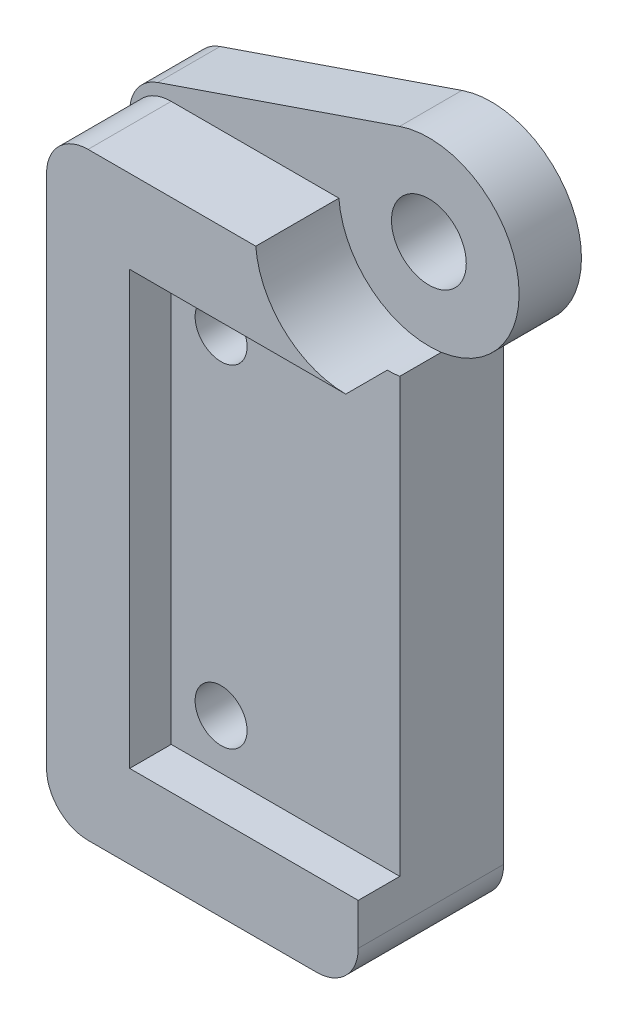
SolidWorks part; units mm, degrees
ref_plane "Front Plane" through (0, 0, 0) normal (0, 0, 1) x (1, 0, 0)
ref_plane "Top Plane" through (0, 0, 0) normal (0, 1, 0) x (1, 0, 0)
ref_plane "Right Plane" through (0, 0, 0) normal (1, 0, 0) x (0, 0, -1)
sketch "Sketch1" plane through (0, 0, 0) normal (0, 0, 1) x (1, 0, 0)
  line L0 (-38, -8) -> (-38, 8) construction
  line L1 (40, -10) -> (-40, -10)
  line L2 (40, -10) -> (40, 10)
  line L3 (40, 10) -> (-40, 10)
  line L4 (-40, -10) -> (-40, 10)
  line L5 (40, -10) -> (-40, 10) construction
  line L6 (40, 10) -> (-40, -10) construction
  line L7 (-40.4, 10.4) -> (-40.4, -10.4)
  line L8 (-40.4, -10.4) -> (-29.4, -10.4)
  line L9 (-29.4, -10.4) -> (-29.4, -14.4)
  line L10 (-29.4, -14.4) -> (-44.4, -14.4)
  line L11 (-44.4, -14.4) -> (-44.4, 14.4)
  line L12 (-44.4, 14.4) -> (-29.4, 14.4)
  line L13 (-29.4, 14.4) -> (-29.4, 10.4)
  line L14 (-29.4, 10.4) -> (-40.4, 10.4)
  line L15 (-29.4, -10.4) -> (-29.4, 10.4)
  line L17 (-44.4, 14.4) -> (-31.4083, 18.8528)
  circle A0 centre (-38, 8) radius 1.25
  circle A1 centre (-38, -8) radius 1.25
  circle A2 centre (-30, 14.7437) radius 1.8
  circle A3 centre (0, -6) radius 2.75 construction
  circle A4 centre (-30, 14.7437) radius 4.3437
  circle A5 centre (-38, 8) radius 2.3
  circle A6 centre (-38, -8) radius 2.3
  point P0 (0, 0)
  point P8 (-38, 0)
  point P13 (-29.4, 0)
  dimension "D5" = 2.5
  dimension "D12" = 3.6
  dimension "D13" = 16
  dimension "D14" = 5.5
  dimension "D15" = 20.7437
  dimension "D16" = 4.6
  dimension "D1" = 16
  dimension "D2" = 38
  dimension "D3" = 80
  dimension "D4" = 20
  dimension "D6" = 0.4
  dimension "D7" = 0.4
  dimension "D8" = 4
  dimension "D9" = 4
  dimension "D10" = 15
  dimension "D11" = 30
extrude "Boss-Extrude1" add sketch "Sketch1" along normal blind 3 contours L14 L13 A2 L12 L11 L10 L9 L8 L7 | A6 L4 A5 L3 L15 L14 L7 L8 L1 | A6 L4 L1 | A6 L1 L15 L3 A5 L4 | L13 L17 L12 A2 | A5 L3 L4 | L12 A4 L13 A2 | A4 L14 L13 | A4 L17 L12 region at (-29.6353, -10.2, 0) region at (-34.1181, 0, 0) region at (-29.7247, -12.4, 0) region at (-39.7386, -9.7386, 0) region at (-29.5499, 10.4125, 0) region at (-39.7386, 9.7386, 0) region at (-31.7182, 12.4313, 0) region at (-29.2774, 11.7441, 0) region at (-37.3258, 15.7206, 0)
extrude "Boss-Extrude2" add sketch "Sketch1<4>" along normal blind 2 from surface contours L14 L13 L12 L11 L10 L9 L8 L7 | A6 L1 L15 L3 A5 L4 | A6 L4 A5 L3 L15 L14 L7 L8 L1 | L3 A5 L4 A0 | L4 A5 | L3 A5 | A5 L3 L4 | A6 L4 L1 | L4 A6 L1 A1 | L4 A6 | L1 A6 | A4 L14 L13 region at (-29.6353, -10.2, 0) region at (-34.1181, 0, 0) region at (-38, -10.1207, 0) region at (-38, -9.9392, 0) region at (-29.7247, -12.4, 0) region at (-39.7386, -9.7386, 0) region at (-36.0648, 9.1265, 0) region at (-38, 10.1207, 0) region at (-29.5499, 10.4125, 0) region at (-40.1207, -8, 0) region at (-39.7386, 9.7386, 0) region at (-40.1207, 8, 0) starting at face at (-35.7, 8, 3)
sketch "Sketch1<4>" plane through (0, 0, 0) normal (0, 0, 1) x (1, 0, 0) same geometry as "Sketch1"
extrude "Boss-Extrude3" add sketch "Sketch1<5>" along normal blind 2 from surface contours A4 L12 L11 L10 L9 L8 L7 L14 region at (-29.7247, -12.4, 0) starting at face at (-36.75, -8, 5)
sketch "Sketch1<5>" plane through (0, 0, 0) normal (0, 0, 1) x (1, 0, 0) same geometry as "Sketch1"
fillet "Fillet1" radius 2 3 edges at (-44.4, 14.4, 5) (-29.4, -14.4, 3.5) (-44.4, -14.4, 3.5) tangent propagation no
fillet "Fillet2" radius 2 1 edges at (-44.4, 14.4, 1.5) tangent propagation no
